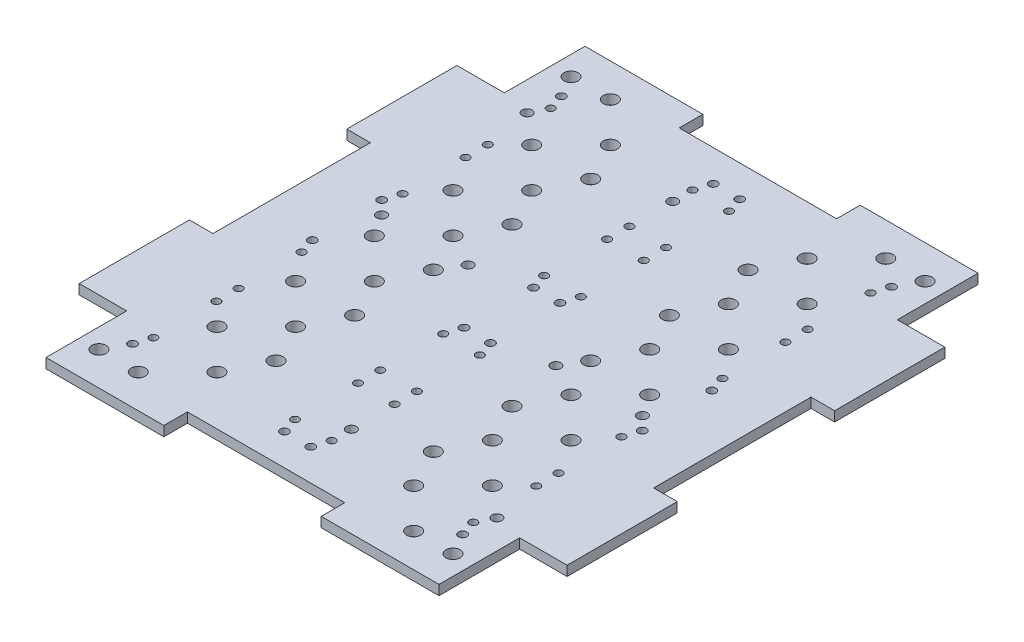
SolidWorks part; units mm, degrees
ref_plane "Front Plane" through (0, 0, 0) normal (0, 0, 1) x (1, 0, 0)
ref_plane "Top Plane" through (0, 0, 0) normal (0, 1, 0) x (1, 0, 0)
ref_plane "Right Plane" through (0, 0, 0) normal (1, 0, 0) x (0, 0, -1)
sketch "Sketch1" plane through (0, 0, 0) normal (0, 1, 0) x (1, 0, 0)
  line L0 (-25.4, 86.995) -> (-63.4314, 86.995)
  line L1 (-88.9, -101.6) -> (88.9, -101.6) construction
  line L2 (101.6, -88.9) -> (101.6, 88.9) construction
  line L3 (88.9, 101.6) -> (-88.9, 101.6) construction
  line L4 (-78.74, -60.96) -> (-63.4314, -60.96)
  line L5 (-63.4314, -60.96) -> (-63.4314, -86.995)
  line L6 (-63.4314, -86.995) -> (-25.4, -86.995)
  line L7 (63.4314, -86.995) -> (63.4314, -60.96)
  line L8 (63.4314, -60.96) -> (78.74, -60.96)
  line L9 (78.74, -60.96) -> (78.74, -25.4)
  line L10 (78.74, 60.96) -> (63.4314, 60.96)
  line L11 (63.4314, 60.96) -> (63.4314, 86.995)
  line L12 (63.4314, 86.995) -> (25.4, 86.995)
  line L13 (-63.4314, 86.995) -> (-63.4314, 60.96)
  line L14 (-63.4314, 60.96) -> (-78.74, 60.96)
  line L15 (-78.74, 60.96) -> (-78.74, 25.4)
  line L16 (-78.74, -25.4) -> (-78.74, -60.96)
  line L17 (-78.74, -25.4) -> (-71.12, -25.4)
  line L19 (-78.74, 25.4) -> (-71.12, 25.4)
  line L20 (-71.12, -25.4) -> (-71.12, 25.4)
  line L22 (-25.4, 86.995) -> (-25.4, 79.375)
  line L23 (-25.4, 79.375) -> (25.4, 79.375)
  line L24 (25.4, 86.995) -> (25.4, 79.375)
  line L25 (78.74, 25.4) -> (71.12, 25.4)
  line L27 (78.74, -25.4) -> (71.12, -25.4)
  line L28 (71.12, 25.4) -> (71.12, -25.4)
  line L30 (25.4, -86.995) -> (25.4, -79.375)
  line L31 (25.4, -79.375) -> (-25.4, -79.375)
  line L32 (-25.4, -86.995) -> (-25.4, -79.375)
  line L33 (78.74, 25.4) -> (78.74, 60.96)
  line L34 (25.4, -86.995) -> (63.4314, -86.995)
  line L35 (-101.6, 88.9) -> (-101.6, -88.9) construction
  arc A0 (88.9, -101.6) -> (101.6, -88.9) centre (88.9, -88.9) ccw construction
  arc A1 (-101.6, -88.9) -> (-88.9, -101.6) centre (-88.9, -88.9) ccw construction
  arc A2 (101.6, 88.9) -> (88.9, 101.6) centre (88.9, 88.9) ccw construction
  arc A3 (-101.6, 88.9) -> (-88.9, 101.6) centre (-88.9, 88.9) cw construction
  circle A4 centre (-57.15, 76.2) radius 2.286
  circle A5 centre (57.15, 76.2) radius 2.286
  circle A6 centre (57.15, -76.2) radius 2.286
  circle A7 centre (-57.15, -76.2) radius 2.286
  point P3 (0, 101.6)
  point P5 (101.6, 0)
  point P13 (101.6, 101.6)
  point P16 (-101.6, 101.6)
  point P38 (-71.12, 0)
  point P55 (0, -79.375)
  point P56 (0, 79.375)
  point P57 (71.12, 0)
  dimension "D2" = 12.7
  dimension "D11" = 4.572
  dimension "D8" = 44.45
  dimension "D1" = 203.2
  dimension "D3" = 203.2
  dimension "D4" = 22.86
  dimension "D5" = 15.3086
  dimension "D6" = 35.56
  dimension "D7" = 173.99
  dimension "D12" = 50.8
  dimension "D13" = 25.4
  dimension "D14" = 44.45
  dimension "D15" = 25.4
  dimension "D18" = 7.62
extrude "Boss-Extrude1" add sketch "Sketch1" along normal blind 3.175
sketch "Sketch2" plane through (0, 3.175, 0) normal (0, 1, 0) x (1, 0, 0)
  line L0 (-25.4, -79.375) -> (25.4, -79.375) construction
  line L2 (-63.4314, -60.96) -> (-63.4314, -86.995) construction
  line L3 (0, 0) -> (0, 50000) construction
  line L4 (-1000, 0) -> (49000, 0) construction
  circle A0 centre (-53.2714, -69.215) radius 1.35
  circle A1 centre (-4.2714, -69.215) radius 1.35
  circle A2 centre (-4.2714, -11.215) radius 1.35
  circle A3 centre (-53.2714, -11.215) radius 1.35
  circle A4 centre (53.2714, -11.215) radius 1.35
  circle A5 centre (4.2714, -11.215) radius 1.35
  circle A6 centre (4.2714, -69.215) radius 1.35
  circle A7 centre (53.2714, -69.215) radius 1.35
  circle A8 centre (53.2714, 11.215) radius 1.35
  circle A9 centre (53.2714, 69.215) radius 1.35
  circle A10 centre (4.2714, 69.215) radius 1.35
  circle A11 centre (4.2714, 11.215) radius 1.35
  circle A12 centre (-4.2714, 11.215) radius 1.35
  circle A13 centre (-4.2714, 69.215) radius 1.35
  circle A14 centre (-53.2714, 11.215) radius 1.35
  circle A15 centre (-53.2714, 69.215) radius 1.35
  dimension "D1" = 2.7
  dimension "D2" = 58
  dimension "D3" = 49
  dimension "D4" = 10.16
  dimension "D5" = 10.16
extrude "Raspberry Pi Holes" cut sketch "Sketch2" against normal through all
sketch "Sketch3" plane through (0, 3.175, 0) normal (0, 1, 0) x (1, 0, 0)
  line L0 (-53.2714, -11.215) -> (-4.2714, -11.215) construction
  line L1 (-51.6314, -43.815) -> (-5.9114, -43.815) construction
  line L2 (-1000, 0) -> (49000, 0) construction
  line L3 (0, -1000) -> (0, 49000) construction
  line L4 (51.6314, -43.815) -> (5.9114, -43.815) construction
  line L5 (53.2714, -11.215) -> (4.2714, -11.215) construction
  line L6 (53.2714, 11.215) -> (4.2714, 11.215) construction
  line L7 (51.6314, 43.815) -> (5.9114, 43.815) construction
  line L8 (-51.6314, 43.815) -> (-5.9114, 43.815) construction
  line L9 (-53.2714, 11.215) -> (-4.2714, 11.215) construction
  circle A0 centre (-51.6314, -64.135) radius 1.27
  circle A1 centre (-5.9114, -64.135) radius 1.27
  circle A2 centre (-5.9114, -43.815) radius 1.27
  circle A3 centre (-51.6314, -43.815) radius 1.27
  circle A4 centre (-53.2714, -69.215) radius 1.35 construction
  circle A5 centre (-51.6314, -16.295) radius 1.27
  circle A6 centre (-51.6314, -36.615) radius 1.27
  circle A7 centre (-5.9114, -36.615) radius 1.27
  circle A8 centre (-5.9114, -16.295) radius 1.27
  circle A9 centre (-53.2714, -11.215) radius 1.35 construction
  circle A10 centre (5.9114, -16.295) radius 1.27
  circle A11 centre (5.9114, -36.615) radius 1.27
  circle A12 centre (51.6314, -36.615) radius 1.27
  circle A13 centre (51.6314, -16.295) radius 1.27
  circle A14 centre (51.6314, -43.815) radius 1.27
  circle A15 centre (5.9114, -43.815) radius 1.27
  circle A16 centre (5.9114, -64.135) radius 1.27
  circle A17 centre (51.6314, -64.135) radius 1.27
  circle A18 centre (51.6314, 64.135) radius 1.27
  circle A19 centre (5.9114, 64.135) radius 1.27
  circle A20 centre (5.9114, 43.815) radius 1.27
  circle A21 centre (51.6314, 43.815) radius 1.27
  circle A22 centre (51.6314, 16.295) radius 1.27
  circle A23 centre (51.6314, 36.615) radius 1.27
  circle A24 centre (5.9114, 36.615) radius 1.27
  circle A25 centre (5.9114, 16.295) radius 1.27
  circle A26 centre (-5.9114, 16.295) radius 1.27
  circle A27 centre (-5.9114, 36.615) radius 1.27
  circle A28 centre (-51.6314, 36.615) radius 1.27
  circle A29 centre (-51.6314, 16.295) radius 1.27
  circle A30 centre (-51.6314, 43.815) radius 1.27
  circle A31 centre (-5.9114, 43.815) radius 1.27
  circle A32 centre (-5.9114, 64.135) radius 1.27
  circle A33 centre (-51.6314, 64.135) radius 1.27
  point P8 (-28.7714, -43.815)
  point P9 (-28.7714, -11.215)
  dimension "D1" = 2.54
  dimension "D2" = 45.72
  dimension "D3" = 20.32
  dimension "D4" = 5.08
  dimension "D6" = 5.08
  dimension "D5" = 2
extrude "Feather Board Holes" cut sketch "Sketch3" against normal through all
sketch "Sketch4" plane through (0, 3.175, 0) normal (0, 1, 0) x (1, 0, 0)
  circle A3 centre (5.9114, -57.785) radius 1.6
  circle A4 centre (21.1514, -6.985) radius 1.6
  circle A5 centre (49.0914, -6.985) radius 1.6
  circle A6 centre (54.1714, -59.055) radius 1.6
  circle A8 centre (5.9114, -64.135) radius 1.27 construction
  point P10 (53.2714, -64.135)
  point P15 (5.9114, -64.135)
  dimension "D4" = 5.08
  dimension "D5" = 3.2
  dimension "D6" = 6.35
  dimension "D7" = 1.27
  dimension "D1" = 50.8
  dimension "D2" = 27.94
  dimension "D3" = 15.24
extrude "Arduino Uno 1" cut sketch "Sketch4" against normal through all
sketch "Sketch5" plane through (0, 3.175, 0) normal (0, 1, 0) x (1, 0, 0)
  circle A0 centre (-5.9114, 57.785) radius 1.6
  circle A1 centre (-54.1714, 59.055) radius 1.6
  circle A2 centre (-49.0914, 6.985) radius 1.6
  circle A3 centre (-21.1514, 6.985) radius 1.6
  circle A5 centre (-5.9114, 64.135) radius 1.27 construction
  point P8 (-54.1714, 62.1936)
  point P9 (-5.9114, 64.135)
  dimension "D1" = 3.2
  dimension "D2" = 50.8
  dimension "D3" = 15.24
  dimension "D4" = 27.94
  dimension "D5" = 5.08
  dimension "D6" = 6.35
  dimension "D7" = 1.27
extrude "Arduino Uno 2" cut sketch "Sketch5" against normal through all
sketch "Sketch6" plane through (0, 3.175, 0) normal (0, 1, 0) x (1, 0, 0)
  line L0 (44.45, 76.2) -> (-44.45, 76.2) construction
  line L1 (25.4, 79.375) -> (-25.4, 79.375) construction
  line L4 (44.45, 76.2) -> (44.4157, 86.995) construction
  line L6 (63.4314, 86.995) -> (25.4, 86.995) construction
  line L8 (44.45, -76.2) -> (44.4157, -86.995) construction
  line L9 (25.4, -86.995) -> (63.4314, -86.995) construction
  circle A0 centre (44.45, 76.2) radius 2.286
  circle A1 centre (-44.45, 76.2) radius 2.286
  circle A3 centre (44.45, 50.8) radius 2.286
  circle A4 centre (-44.45, 50.8) radius 2.286
  circle A5 centre (44.45, 25.4) radius 2.286
  circle A6 centre (-44.45, 25.4) radius 2.286
  circle A7 centre (44.45, 0) radius 2.286
  circle A8 centre (-44.45, 0) radius 2.286
  circle A9 centre (44.45, -25.4) radius 2.286
  circle A10 centre (-44.45, -25.4) radius 2.286
  circle A11 centre (44.45, -50.8) radius 2.286
  circle A12 centre (-44.45, -50.8) radius 2.286
  circle A13 centre (44.45, -76.2) radius 2.286
  circle A14 centre (-44.45, -76.2) radius 2.286
  point P4 (0, 76.2)
  point P7 (0, 79.375)
  dimension "D1" = 4.572
  dimension "D2" = 88.9
  dimension "D4" = 25.4
  dimension "D3" = 7
extrude "Custom PCB 3 inch" cut sketch "Sketch6" against normal through all
sketch "Sketch7" plane through (0, 3.175, 0) normal (0, 1, 0) x (1, 0, 0)
  line L0 (-31.75, -63.5) -> (31.75, -63.5) construction
  line L5 (-25.4, -79.375) -> (25.4, -79.375) construction
  line L6 (-31.75, 63.5) -> (31.75, 63.5) construction
  line L7 (0, 63.5) -> (0, 79.375) construction
  line L8 (25.4, 79.375) -> (-25.4, 79.375) construction
  line L9 (0, -63.5) -> (0, -79.375) construction
  circle A0 centre (-31.75, -63.5) radius 2.286
  circle A1 centre (31.75, -63.5) radius 2.286
  circle A2 centre (31.75, -38.1) radius 2.286
  circle A3 centre (-31.75, -38.1) radius 2.286
  circle A4 centre (31.75, -12.7) radius 2.286
  circle A5 centre (-31.75, -12.7) radius 2.286
  circle A6 centre (31.75, 12.7) radius 2.286
  circle A7 centre (-31.75, 12.7) radius 2.286
  circle A8 centre (31.75, 38.1) radius 2.286
  circle A9 centre (-31.75, 38.1) radius 2.286
  circle A10 centre (31.75, 63.5) radius 2.286
  circle A11 centre (-31.75, 63.5) radius 2.286
  point P4 (0, -63.5)
  point P7 (0, -79.375)
  dimension "D1" = 4.572
  dimension "D2" = 63.5
  dimension "D3" = 6
  dimension "D4" = 25.4
extrude "Custom PCB 2.5 inch" cut sketch "Sketch7" against normal through all
sketch "Sketch8" plane through (0, 3.175, 0) normal (0, 1, 0) x (1, 0, 0)
  line L0 (-25.4, -50.8) -> (25.4, -50.8) construction
  line L1 (-25.4, -79.375) -> (25.4, -79.375) construction
  line L2 (-25.4, -25.4) -> (25.4, -25.4) construction
  line L3 (-25.4, 0) -> (25.4, 0) construction
  line L4 (-25.4, 25.4) -> (25.4, 25.4) construction
  line L5 (-25.4, 50.8) -> (25.4, 50.8) construction
  line L6 (0, 50.8) -> (0, 79.375) construction
  line L7 (25.4, 79.375) -> (-25.4, 79.375) construction
  line L8 (0, -50.8) -> (0, -79.375) construction
  circle A0 centre (-25.4, -50.8) radius 2.286
  circle A1 centre (25.4, -50.8) radius 2.286
  circle A2 centre (-25.4, -25.4) radius 2.286
  circle A3 centre (25.4, -25.4) radius 2.286
  circle A4 centre (-25.4, 0) radius 2.286
  circle A5 centre (25.4, 0) radius 2.286
  circle A6 centre (-25.4, 25.4) radius 2.286
  circle A7 centre (25.4, 25.4) radius 2.286
  circle A8 centre (-25.4, 50.8) radius 2.286
  circle A9 centre (25.4, 50.8) radius 2.286
  point P4 (0, -50.8)
  point P7 (0, -79.375)
  dimension "D1" = 50.8
  dimension "D2" = 4.572
  dimension "D4" = 25.4
  dimension "D3" = 5
extrude "Custom PCB 2 inch" cut sketch "Sketch8" against normal through all
